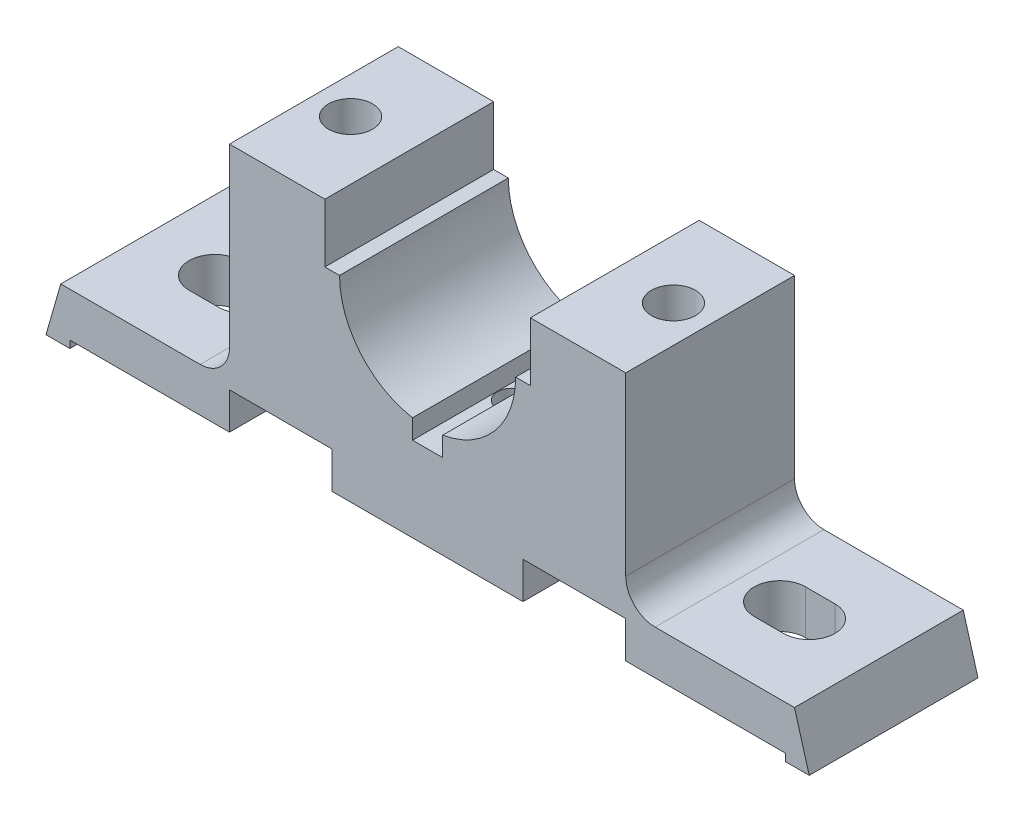
SolidWorks part; units mm, degrees
ref_plane "Front Plane" through (0, 0, 0) normal (0, 0, 1) x (1, 0, 0)
ref_plane "Top Plane" through (0, 0, 0) normal (0, 1, 0) x (1, 0, 0)
ref_plane "Right Plane" through (0, 0, 0) normal (1, 0, 0) x (0, 0, -1)
sketch "Sketch1" plane through (0, 0, 0) normal (0, 0, 1) x (1, 0, 0)
  line L0 (0, 0) -> (0, 21.7138) construction
  line L1 (-24, 0) -> (-28, 0)
  line L2 (-28, 0) -> (-28, 16)
  line L3 (-28, 16) -> (-54, 16)
  line L4 (-54, 16) -> (-54, -32)
  line L5 (-62, -40) -> (-99.9856, -40)
  line L6 (-99.9856, -40) -> (-104, -54)
  line L7 (-104, -54) -> (-97.5, -54)
  line L8 (-97.5, -54) -> (-97.5, -52)
  line L9 (-97.5, -52) -> (26, -52)
  line L10 (26, -52) -> (26, -42)
  line L11 (26, -42) -> (54, -42)
  line L12 (54, -42) -> (54, -52)
  line L13 (54, -52) -> (-59.0346, -52)
  line L14 (-54, -52) -> (54, -52)
  line L15 (-54, -42) -> (-54, -52)
  line L16 (-26, -42) -> (-54, -42)
  line L17 (-26, -52) -> (-26, -42)
  line L18 (97.5, -52) -> (-26, -52)
  line L19 (97.5, -54) -> (97.5, -52)
  line L20 (104, -54) -> (97.5, -54)
  line L21 (99.9856, -40) -> (104, -54)
  line L22 (62, -40) -> (99.9856, -40)
  line L23 (54, 16) -> (54, -32)
  line L24 (28, 16) -> (54, 16)
  line L25 (28, 0) -> (28, 16)
  line L26 (24, 0) -> (28, 0)
  line L28 (-4.1051, -23.6463) -> (-4.1051, -28.9534)
  line L29 (4.1051, -23.6463) -> (4.1051, -28.9534)
  line L30 (-4.1051, -28.9534) -> (4.1051, -28.9534)
  arc A0 (-24, 0) -> (-4.1051, -23.6463) centre (0, 0) ccw
  arc A1 (-54, -32) -> (-62, -40) centre (-62, -32) cw
  arc A2 (54, -32) -> (62, -40) centre (62, -32) ccw
  arc A3 (4.1051, -23.6463) -> (24, 0) centre (0, 0) ccw
  dimension "D1" = 48
  dimension "D3" = 8
  dimension "D2" = 4
  dimension "D4" = 106
  dimension "D5" = 2
  dimension "D6" = 28
  dimension "D7" = 16
  dimension "D8" = 56
  dimension "D9" = 10
  dimension "D10" = 10
  dimension "D11" = 14
  dimension "D12" = 208
  dimension "D13" = 195
  dimension "D14" = 54
  dimension "D15" = 108
extrude "Boss-Extrude1" add sketch "Sketch1" along normal mid plane 46 contours A3 L29 L30 L28 A0 L1 L2 L3 L4 A1 L5 L6 L7 L8 L9 L15 L16 L17 L14 L10 L11 L12 L18 L19 L20 L21 L22 A2 L23 L24 L25 L26 region at (-20.044, -16.8641, 0)
sketch "Sketch2" plane through (0, 0, 0) normal (0, 1, 0) x (1, 0, 0)
  line L0 (-81, 0) -> (-73, 0) construction
  line L1 (-81, 7) -> (-73, 7)
  line L2 (-81, -7) -> (-73, -7)
  line L3 (0, 0) -> (0, -42.7134) construction
  line L4 (81, 0) -> (73, 0) construction
  line L5 (81, 7) -> (73, 7)
  line L6 (81, -7) -> (73, -7)
  line L7 (-28, -23) -> (-28, 23) construction
  arc A0 (-81, 7) -> (-81, -7) centre (-81, 0) ccw
  arc A1 (-73, -7) -> (-73, 7) centre (-73, 0) ccw
  circle A2 centre (0, 0) radius 4
  circle A3 centre (-44, 0) radius 6
  circle A4 centre (44, 0) radius 6
  arc A5 (81, 7) -> (81, -7) centre (81, 0) cw
  arc A6 (73, -7) -> (73, 7) centre (73, 0) cw
  point P3 (-77, 0)
  point P17 (77, 0)
  dimension "D2" = 7
  dimension "D3" = 8
  dimension "D4" = 12
  dimension "D6" = 16
  dimension "D1" = 8
  dimension "D5" = 154
extrude "Cut-Extrude1" cut sketch "Sketch2" against normal through all both and the other way through all contours L2 A1 L1 A0 | A6 L6 A5 L5 | A4 | A3 | A3 | A4 region at (-77, 0, 0) region at (77, 0, 0) region at (-44, 0, 0) region at (44, 0, 0)
extrude "Cut-Extrude4" cut sketch "Sketch2<3>" against normal blind 8 from surface contours A2 region at (0, 0, 0) starting at face at (0, -28.9534, 0)
sketch "Sketch2<3>" plane through (0, 0, 0) normal (0, 1, 0) x (1, 0, 0) same geometry as "Sketch2"
